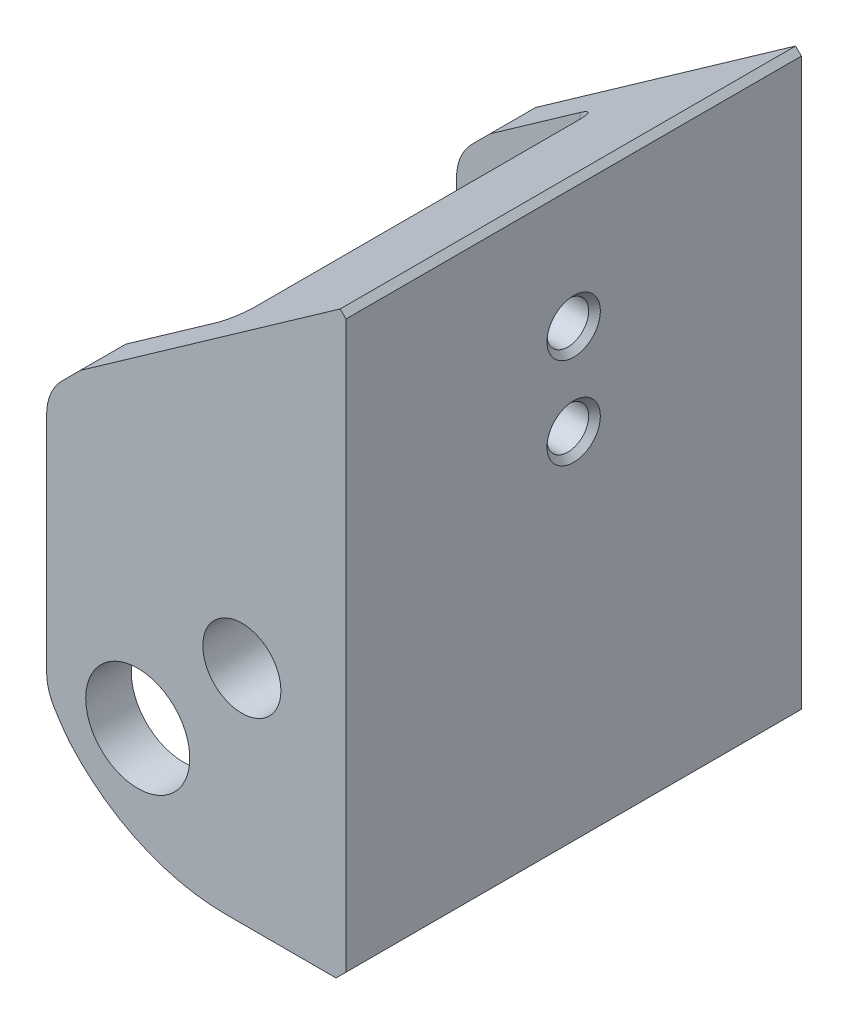
SolidWorks part; units mm, degrees
note: The reader was unsure of these and kept them because the rebuilt part matched: shared geometry of "Sketch2<3>".
ref_plane "Front Plane" through (0, 0, 0) normal (0, 0, 1) x (1, 0, 0)
ref_plane "Top Plane" through (0, 0, 0) normal (0, 1, 0) x (1, 0, 0)
ref_plane "Right Plane" through (0, 0, 0) normal (1, 0, 0) x (0, 0, -1)
sketch "Sketch1" plane through (0, 0, 0) normal (0, 0, 1) x (1, 0, 0)
  line L0 (-7.2764, -10.5186) -> (2.2236, -16.0034)
  line L1 (2.2236, -16.0034) -> (6.2236, -16.0034)
  line L2 (-7.2764, -10.5186) -> (-7.2764, -0.5186)
  line L4 (6.2236, -16.0034) -> (6.2236, 8.9966)
  line L5 (-7.2764, -10.5186) -> (6.2236, 8.9966) construction
  line L6 (-1.4071, 3.6183) -> (6.2236, -16.0034) construction
  line L7 (-7.2764, -0.5186) -> (6.2236, 8.9966)
  point P0 (0, 0)
  dimension "D1" = 13.5
  dimension "D2" = 25
  dimension "D3" = 4
  dimension "D4" = 30
  dimension "D5" = 10
extrude "Boss-Extrude1" add sketch "Sketch1" along normal blind 17.5
sketch "Sketch2" plane through (0, 0, 0) normal (0, 0, -1) x (-1, 0, 0)
  line L0 (7.2764, -0.5186) -> (7.2764, -10.5186) construction
  line L1 (-6.2236, -16.0034) -> (-6.2236, 8.9966) construction
  line L3 (-2.2236, -16.0034) -> (-6.2236, -16.0034) construction
  circle A0 centre (1.7764, -9.0034) radius 2
  circle A1 centre (-2.2236, -5.0034) radius 1.5
  dimension "D1" = 4
  dimension "D2" = 3
  dimension "D3" = 5.5
  dimension "D4" = 4
  dimension "D5" = 7
  dimension "D6" = 11
extrude "Cut-Extrude1" cut sketch "Sketch2" against normal through all contours A0
extrude "Cut-Extrude2" cut sketch "Sketch2<3>" against normal blind 7 contours A1
sketch "Sketch2<3>" plane through (0, 0, 0) normal (0, 0, -1) x (-1, 0, 0) same geometry as "Sketch2"
sketch "Sketch5" plane through (0, 0, 0) normal (0, 0, -1) x (-1, 0, 0)
  line L0 (-6.2236, -13.5034) -> (2.1066, -13.5034)
  line L1 (-6.2236, -16.0034) -> (-6.2236, 8.9966) construction
  line L2 (7.2764, -10.5186) -> (-2.2236, -16.0034) construction
  line L3 (2.1066, -13.5034) -> (-2.2236, -16.0034)
  line L4 (-2.2236, -16.0034) -> (-6.2236, -16.0034)
  line L5 (-6.2236, -16.0034) -> (-6.2236, -13.5034)
  dimension "D1" = 2.5
extrude "Cut-Extrude3" cut sketch "Sketch5" against normal through all
sketch "Sketch6" plane through (0, 0, 0) normal (0, 0, -1) x (-1, 0, 0)
  line L0 (2.1066, -13.5034) -> (7.2764, -7.3422)
  line L1 (7.2764, -0.5186) -> (7.2764, -10.5186) construction
  line L2 (7.2764, -7.3422) -> (7.2764, -10.5186)
  line L3 (7.2764, -10.5186) -> (2.1066, -13.5034)
  dimension "D1" = 20
extrude "Cut-Extrude4" cut sketch "Sketch6" against normal through all
sketch "Sketch7" plane through (6.2236, 0, 0) normal (1, 0, 0) x (0, 0, -1)
  line L0 (-8.75, 8.9966) -> (-8.75, -14.2492) construction
  line L1 (-17.5, 8.9966) -> (0, 8.9966) construction
  line L11 (-17.5, -13.5034) -> (0, -13.5034) construction
  line L12 (-15.75, -13.5034) -> (-1.75, -13.5034)
  line L13 (-15.75, -13.5034) -> (-15.75, -6.7534)
  line L14 (-15.75, -6.7534) -> (-1.75, -6.7534)
  line L15 (-1.75, -13.5034) -> (-1.75, -6.7534)
  dimension "D1" = 7
  dimension "D2" = 6.75
  dimension "D3" = 7
extrude "Cut-Extrude5" cut sketch "Sketch7" against normal through all
sketch "Sketch11" plane through (0, -6.7534, 0) normal (0, -1, 0) x (1, 0, 0)
  line L0 (-7.2764, 15.75) -> (-7.2764, 1.75) construction
  line L1 (-7.2764, 15.75) -> (0.2236, 15.75)
  line L2 (-7.2764, 15.75) -> (-7.2764, 1.75)
  line L3 (-7.2764, 1.75) -> (0.2236, 1.75)
  line L4 (0.2236, 15.75) -> (0.2236, 1.75)
  line L5 (-7.2764, 15.75) -> (6.2236, 15.75) construction
  line L6 (-7.2764, 1.75) -> (6.2236, 1.75) construction
  dimension "D1" = 7.5
extrude "Cut-Extrude6" cut sketch "Sketch11" against normal through all
hole_wizard "M2x0.4 Tapped Hole1" positions "Sketch9" profile "Sketch10" tap size "M2x0.4" standard "ANSI Metric"
sketch "Sketch9" plane through (6.2236, 0, 0) normal (1, 0, 0) x (0, 0, -1)
  line L2 (0, -13.5034) -> (0, 8.9966) construction
  line L3 (-17.5, -13.5034) -> (-17.5, 8.9966) construction
  line L4 (-17.5, 8.9966) -> (0, 8.9966) construction
  point P0 (-8.75, 3.9966)
  point P2 (-8.75, 0.4966)
  dimension "D1" = 8.75
  dimension "D2" = 3.5
  dimension "D3" = 8.75
  dimension "D4" = 5
cosmetic thread "Hole Thread1" parameters "D1"=6.07, "D2"=2
cosmetic thread "Hole Thread2" parameters "D1"=6.07, "D2"=2
sketch "Sketch10" plane through (6.2236, 3.9966, 8.75) normal (0, 1, 0) x (0, 0, -1)
  line L0 (0, 0) -> (0, 4.4807)
  line L1 (0, 4.4807) -> (0.8, 4)
  line L2 (0.8, 4) -> (0.8, 0.225)
  line L3 (0.8, 0.225) -> (1.025, 0)
  line L5 (1.025, 0) -> (0, 0)
  line L6 (-0.8, 0.225) -> (-1.025, 0) construction
  line L10 (0, 4.4807) -> (-0.8, 4) construction
  line L11 (0, -6.35) -> (0, 107.95) construction
  dimension "Tap Drill Dia." = 1.6
  dimension "Tap Drill Depth" = 4
  dimension "Near C'Sink Dia." = 2.05
  dimension "Near C'Sink Angle" = 90
  dimension "Drill Angle" = 118
sketch "Sketch12" plane through (0, 0, 17.5) normal (0, 0, 1) x (1, 0, 0)
  line L0 (6.2236, -13.5034) -> (6.2236, 8.9966) construction
  line L1 (-2.1066, -13.5034) -> (6.2236, -13.5034) construction
  circle A0 centre (2.2236, -5.0034) radius 1.5
  dimension "D1" = 3
  dimension "D2" = 4
  dimension "D3" = 8.5
extrude "Cut-Extrude7" cut sketch "Sketch12" against normal blind 7
sketch "Sketch13" plane through (0, 0, 17.5) normal (0, 0, 1) x (1, 0, 0)
  line L0 (-6.1289, -8.7098) -> (-6.1289, 0.2902)
  line L1 (-7.2764, -7.3422) -> (-2.1066, -13.5034) construction
  line L2 (6.2236, 8.9966) -> (-7.2764, -0.5186) construction
  line L3 (-6.1289, 0.2902) -> (-7.2764, -0.5186)
  line L4 (-7.2764, -0.5186) -> (-7.2764, -7.3422)
  line L5 (-7.2764, -7.3422) -> (-6.1289, -8.7098)
  dimension "D1" = 9
extrude "Cut-Extrude8" cut sketch "Sketch13" against normal through all
fillet "Fillet1" radius 8 4 edges at (-6.1289, -8.7098, 0.875) (-2.1066, -13.5034, 0.875) (-6.1289, -8.7098, 16.625) (-2.1066, -13.5034, 16.625)
sketch "Sketch14" plane through (6.2236, 0, 0) normal (1, 0, 0) x (0, 0, -1)
  line L0 (-1.75, -13.5034) -> (-1.75, -6.7534) construction
  line L1 (-15.75, -13.5034) -> (-15.75, -6.7534) construction
  line L2 (-15.75, -6.7534) -> (-1.75, -6.7534) construction
  line L3 (-1.75, -13.5034) -> (-1.75, -6.7534)
  line L4 (-15.75, -13.5034) -> (-15.75, -6.7534)
  line L5 (-15.75, -6.7534) -> (-1.75, -6.7534)
  line L6 (-15.75, -13.5034) -> (-1.75, -13.5034)
extrude "Boss-Extrude2" add sketch "Sketch14" against normal blind 4
sketch "Sketch15" plane through (0, 0, 0) normal (0, 0, -1) x (-1, 0, 0)
  line L0 (6.1289, -5.798) -> (6.1289, 0.2902) construction
  line L1 (6.1289, 8.9966) -> (5.2789, 8.9966)
  line L2 (6.1289, 8.9966) -> (6.1289, -13.5034)
  line L3 (6.1289, -13.5034) -> (5.2789, -13.5034)
  line L4 (5.2789, 8.9966) -> (5.2789, -13.5034)
  line L5 (-1.6239, -13.5034) -> (-2.2236, -13.5034) construction
  dimension "D1" = 0.85
extrude "Cut-Extrude9" cut sketch "Sketch15" against normal up to surface (17.5 mm away) up to face at (3.7236, -5.0034, 17.5)
fillet "Fillet2" radius 0.762 5 edges at (2.2236, -10.1284, 1.75) (2.2236, -10.1284, 15.75) (2.2236, -6.7534, 8.75) (0.2236, -0.9929, 15.75) (0.2236, -0.9929, 1.75)
fillet "Fillet3" radius 1.5 4 edges at (2.0004, -6.9766, 1.9732) (2.0004, -6.9766, 15.5268) (0.4616, -6.7534, 15.75) (0.4616, -6.7534, 1.75)
chamfer "Chamfer1" distance 0.381 angle 45 4 edges at (6.2236, -13.5034, 8.75) (6.2236, 8.9966, 8.75) (-5.2789, 0.8893, 16.625) (-5.2789, 0.8893, 0.875) first distance on face at (6.2236, 3.9966, 7.725) first distance on face at (-5.2789, -4.2486, 16.625) first distance on face at (-5.2789, -4.2486, 0.875)
fillet "Fillet4" radius 2 4 edges at (-5.2789, -9.3865, 16.625) (-5.2789, -9.3865, 0.875) (-5.2789, 0.5083, 0.875) (-5.2789, 0.5083, 16.625)
